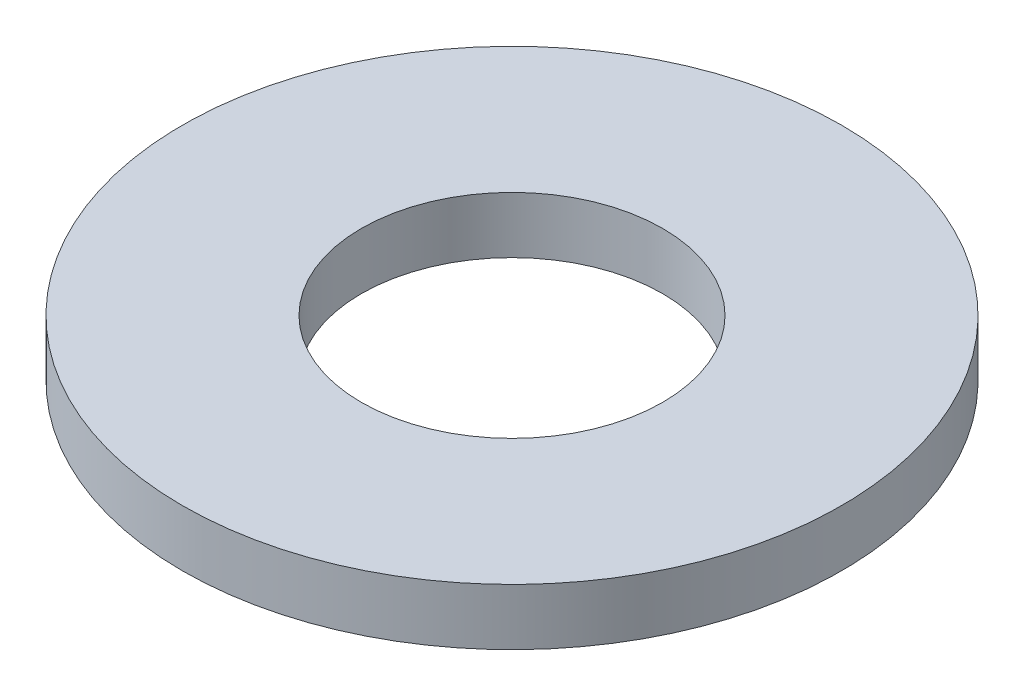
SolidWorks part; units mm, degrees
ref_plane "Plan1" through (0, 0, 0) normal (0, 0, 1) x (1, 0, 0)
ref_plane "Plan2" through (0, 0, 0) normal (0, 1, 0) x (1, 0, 0)
ref_plane "Plan3" through (0, 0, 0) normal (1, 0, 0) x (0, 0, -1)
ref_axis "Axe" through (0, 14.4476, 0) along (0, -1, 0)
sketch "Esquisse1" plane through (0, 0, 0) normal (0, 0, 1) x (1, 0, 0)
  line L1 (0, 0) -> (0, 2.5443) construction
  line L2 (3.2, 0) -> (3.2, 1.2)
  line L3 (3.2, 0) -> (7, 0)
  line L4 (7, 0) -> (7, 1.2)
  line L5 (7, 1.2) -> (3.2, 1.2)
  line L6 (3.2, 0) -> (-3.2, 0) construction
  line L7 (7, 0) -> (-7, 0) construction
  dimension "Epaisseur" = 1.2
  dimension "Rint" = 3.2
  dimension "Rext" = 7
  dimension "Diamètre de passage" = 6.4
  dimension "Diamètre extérieur" = 14
revolve "Base" add sketch "Esquisse1" angle 360 about L1
equation "\"Rext@Esquisse1\"=\"Diamètre extérieur@Esquisse1\"/2"
equation "\"Rint@Esquisse1\" = \"Diamètre de passage@Esquisse1\"/2"
